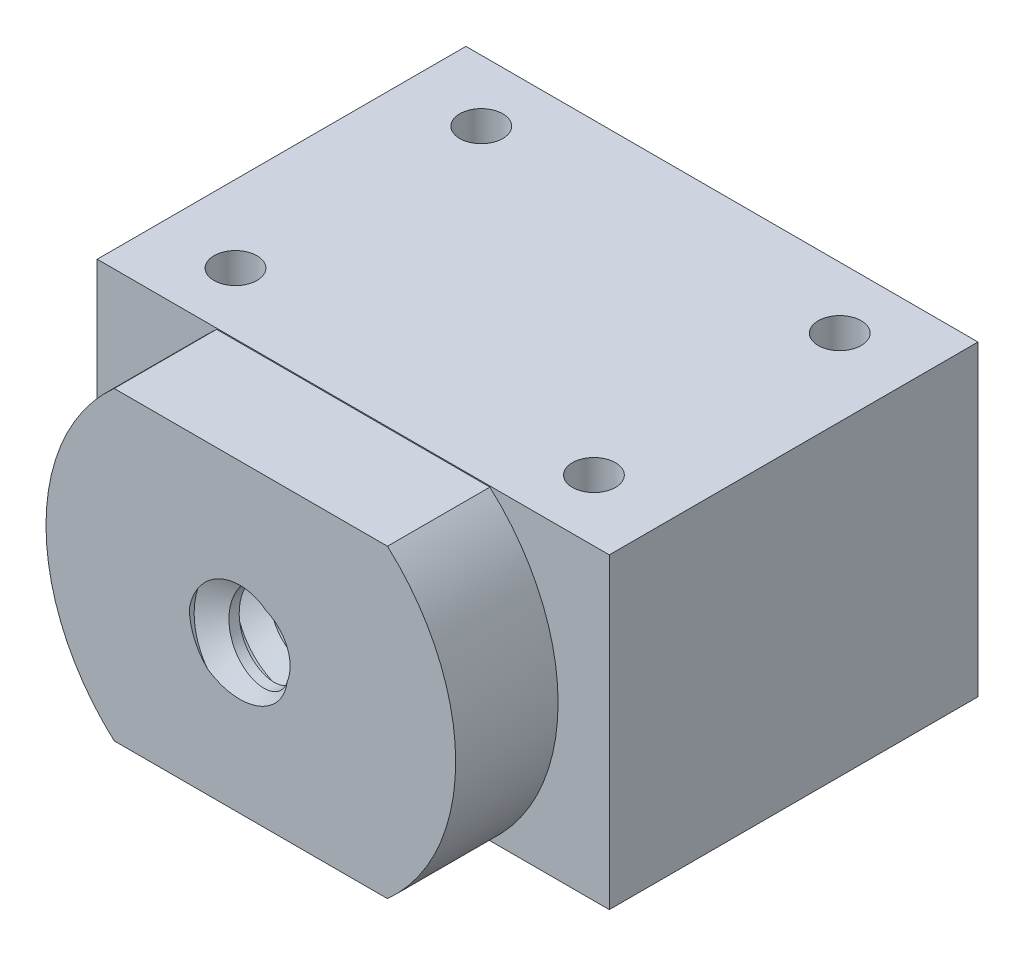
SolidWorks part; units mm, degrees
ref_plane "Front Plane" through (0, 0, 0) normal (0, 0, 1) x (1, 0, 0)
ref_plane "Top Plane" through (0, 0, 0) normal (0, 1, 0) x (1, 0, 0)
ref_plane "Right Plane" through (0, 0, 0) normal (1, 0, 0) x (0, 0, -1)
sketch "Sketch1" plane through (0, 0, 0) normal (0, 0, 1) x (1, 0, 0)
  line L0 (0, 15) -> (0, -15) construction
  line L1 (-25, 15) -> (25, 15)
  line L2 (-25, 15) -> (-25, -15)
  line L3 (-25, -15) -> (25, -15)
  line L4 (25, 15) -> (25, -15)
  line L5 (-25, 15) -> (25, -15) construction
  line L6 (-25, -15) -> (25, 15) construction
  circle A0 centre (0, 0) radius 6
  point P0 (0, 0)
  dimension "D3" = 12
  dimension "D1" = 30
  dimension "D2" = 50
extrude "Boss-Extrude1" add sketch "Sketch1" along normal blind 36
hole_wizard "M5 Tapped Hole1" [suppressed] positions "Sketch2" profile "Sketch3" tap size "M5" standard "ISO"
sketch "Sketch2" plane through (0, 0, 36) normal (0, 0, 1) x (1, 0, 0)
  line L0 (-11.3137, 11.3137) -> (0, 0) construction
  line L2 (0, 0) -> (0, 15) construction
  line L3 (25, 15) -> (-25, 15) construction
  point P0 (-11.3137, 11.3137)
  point P21 (11.3137, 11.3137)
  point P22 (16, 0)
  point P23 (11.3137, -11.3137)
  point P25 (-11.3137, -11.3137)
  point P26 (-16, 0)
  point P28 (-32.0747, 52.2798)
  dimension "D1" = 16
  dimension "D2" = 45
cosmetic thread "Hole Thread1" [suppressed] parameters "D1"=10, "D2"=5
cosmetic thread "Hole Thread2" [suppressed] parameters "D1"=10, "D2"=5
cosmetic thread "Hole Thread3" [suppressed] parameters "D1"=10, "D2"=5
cosmetic thread "Hole Thread4" [suppressed] parameters "D1"=10, "D2"=5
cosmetic thread "Hole Thread5" [suppressed] parameters "D1"=10, "D2"=5
cosmetic thread "Hole Thread6" [suppressed] parameters "D1"=10, "D2"=5
sketch "Sketch3" plane through (-11.3137, 11.3137, 36) normal (1, 0, 0) x (0, -1, 0)
  line L0 (0, 0) -> (0, 11.2618)
  line L1 (0, 11.2618) -> (2.1, 10)
  line L2 (2.1, 10) -> (2.1, 0)
  line L5 (2.1, 0) -> (0, 0)
  line L10 (0, 11.2618) -> (-2.1, 10) construction
  line L11 (0, -6.35) -> (0, 107.95) construction
  dimension "Tap Drill Dia." = 4.2
  dimension "Tap Drill Depth" = 10
  dimension "Drill Angle" = 118
hole_wizard "M5 Tapped Hole2" positions "Sketch4" profile "Sketch5" tap size "M5" standard "ISO"
sketch "Sketch4" plane through (0, 15, 0) normal (0, 1, 0) x (1, 0, 0)
  line L0 (0, 0) -> (0, -36) construction
  line L1 (25, 0) -> (-25, 0) construction
  line L2 (25, -36) -> (-25, -36) construction
  line L4 (-25, -18) -> (25, -18) construction
  line L5 (-25, -36) -> (-25, 0) construction
  line L6 (25, -36) -> (25, 0) construction
  point P0 (-17.5, -6)
  point P10 (17.5, -6)
  point P11 (17.5, -30)
  point P12 (-17.5, -30)
  dimension "D1" = 2
  dimension "D2" = 2
cosmetic thread "Hole Thread7" parameters "D1"=10, "D2"=5
cosmetic thread "Hole Thread8" parameters "D1"=10, "D2"=5
cosmetic thread "Hole Thread9" parameters "D1"=10, "D2"=5
cosmetic thread "Hole Thread10" parameters "D1"=10, "D2"=5
sketch "Sketch5" plane through (-17.5, 15, 6) normal (1, 0, 0) x (0, 0, 1)
  line L0 (0, 0) -> (0, 11.2618)
  line L1 (0, 11.2618) -> (2.1, 10)
  line L2 (2.1, 10) -> (2.1, 0)
  line L5 (2.1, 0) -> (0, 0)
  line L10 (0, 11.2618) -> (-2.1, 10) construction
  line L11 (0, -6.35) -> (0, 107.95) construction
  dimension "Tap Drill Dia." = 4.2
  dimension "Tap Drill Depth" = 10
  dimension "Drill Angle" = 118
sketch "Sketch6" plane through (0, 0, 36) normal (0, 0, 1) x (1, 0, 0)
  line L0 (-13.3413, -14.9) -> (13.3413, -14.9)
  line L1 (-13.3413, 14.9) -> (13.3413, 14.9)
  line L2 (25, 15) -> (-25, 15) construction
  line L3 (-25, -15) -> (25, -15) construction
  arc A0 (-13.3413, 14.9) -> (-13.3413, -14.9) centre (0, 0) ccw
  arc A1 (13.3413, -14.9) -> (13.3413, 14.9) centre (0, 0) ccw
  circle A2 centre (0, 0) radius 6
  dimension "D1" = 20
  dimension "D2" = 12
  dimension "D3" = 0.1
  dimension "D4" = 0.1
extrude "Boss-Extrude3" add sketch "Sketch6" along normal blind 10
sketch "Sketch8" plane through (0, 0, 0) normal (0, 0, -1) x (-1, 0, 0)
  circle A0 centre (0, 0) radius 11
  dimension "D1" = 22
extrude "Cut-Extrude1" cut sketch "Sketch8" against normal blind 6
thread "Thread1" pitch 4 method extrude trim with start face yes trim with end face yes profile "Thread Profile2" start angle 0, offset 6, length 0, pitch 4, diameter 12
ref_plane "Plane2" through (6, 0, 0) normal (0, -1, 0) x (1, 0, 0)
sketch "Thread Profile2" plane through (6, 0, 0) normal (0, -1, 0) x (1, 0, 0)
  line L0 (0, 0) -> (0, 4) construction
  line L11 (0, 0) -> (0, 3.5)
  line L12 (0, 3.5) -> (-2.1651, 2.25)
  line L13 (-2.1651, 2.25) -> (-2.1651, 1.25)
  line L15 (-2.1651, 1.25) -> (0, 0)
  line L17 (-2.1651, 1.75) -> (0, 1.75) construction
  point P2 (0, 0)
  dimension "Pitch" = 4
  dimension "Profile_Angle" = 60
  dimension "Profile_Land" = 1
  dimension "Profile_Height" = 2.1651
